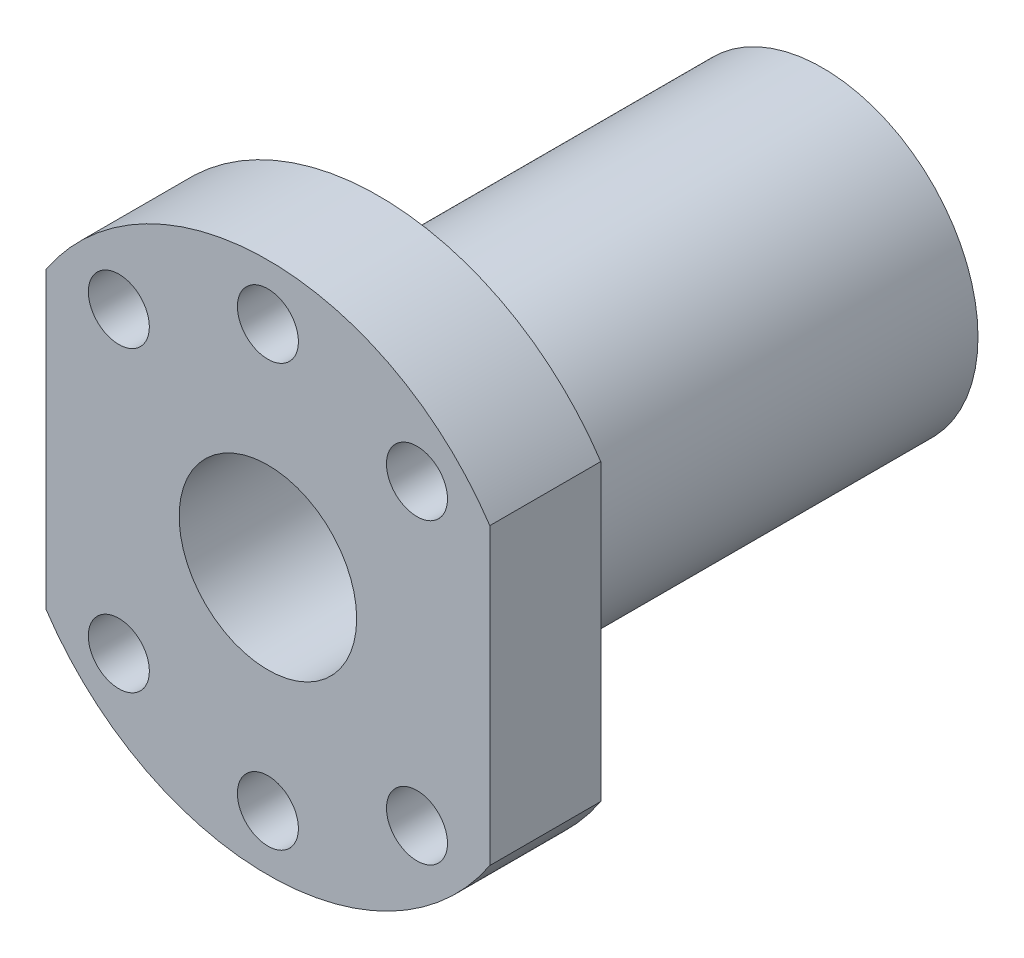
SolidWorks part; units mm, degrees
material "Alloy Steel"
ref_plane "Спереди" through (0, 0, 0) normal (0, 0, 1) x (1, 0, 0)
ref_plane "Сверху" through (0, 0, 0) normal (0, 1, 0) x (1, 0, 0)
ref_plane "Справа" through (0, 0, 0) normal (1, 0, 0) x (0, 0, -1)
sketch "Sketch7" plane through (0, 0, 0) normal (1, 0, 0) x (0, 0, -1)
  line L0 (-22.731, 0) -> (53.4984, 0) construction
  line L1 (0, 8) -> (0, 24)
  line L2 (10, 24) -> (10, 14)
  line L3 (10, 14) -> (50, 14)
  line L4 (50, 14) -> (50, 8)
  line L5 (50, 8) -> (0, 8)
  line L6 (0, 24) -> (10, 24)
  line L7 (5, 19) -> (5, -19) construction
  line L8 (0, 19) -> (10, 19) construction
  point P10 (10, 19)
  point P15 (5, 19)
  point P18 (5, 0)
  dimension "A" = 48
  dimension "L" = 50
  dimension "B" = 10
  dimension "D" = 28
  dimension "dm" = 16
  dimension "W" = 38
revolve "Revolve1" add sketch "Sketch7" angle 360 about L0 other way angle 360
sketch "Sketch8" plane through (0, 0, -10) normal (0, 0, 1) x (1, 0, 0)
  circle A0 centre (0, 0) radius 8 construction
  circle A1 centre (0, 0) radius 8
curve "Helix/Spiral1" pitch 5 height 35 radius 8 centre (0, 0, -10) axis (0, 0, -1) start towards (-0.7071, 0.7071, 0)
ref_plane "Plane1" through (-5.6569, 5.6569, -10) normal (0.7036, 0.7036, -0.099) x (0.7104, -0.6932, 0.1219)
sketch "Sketch9" plane through (-5.6569, 5.6569, -10) normal (0.7036, 0.7036, -0.099) x (0.7104, -0.6932, 0.1219)
  line L0 (0, -2.4488) -> (0, 3.6729) construction
  circle A0 centre (0, 0) radius 1.6
  dimension "D1" = 3.2
sweep "Sweep1" add profiles "Sketch9" path "Helix/Spiral1"
ref_axis "Axis1" through (0, 0, -50) along (0, 0, 1)
sketch "Sketch13" plane through (0, 0, 0) normal (0, 0, 1) x (1, 0, 0)
  line L0 (0, 24) -> (0, -24) construction
  line L1 (-24, 0) -> (24, 0) construction
  line L4 (20, -13.2665) -> (20, 13.2665)
  line L6 (-20, -13.2665) -> (-20, 13.2665)
  circle A0 centre (0, 0) radius 24 construction
  circle A1 centre (0, 0) radius 19 construction
  circle A2 centre (0, 19) radius 2.75
  circle A3 centre (13.435, 13.435) radius 2.75
  circle A4 centre (19, 0) radius 2.75 [skipped]
  circle A5 centre (13.435, -13.435) radius 2.75
  circle A6 centre (0, -19) radius 2.75
  circle A7 centre (-13.435, -13.435) radius 2.75
  circle A8 centre (-19, 0) radius 2.75 [skipped]
  circle A9 centre (-13.435, 13.435) radius 2.75
  arc A10 (20, -13.2665) -> (20, 13.2665) centre (0, 0) ccw
  arc A11 (-20, 13.2665) -> (-20, -13.2665) centre (0, 0) ccw
  point P29 (0, 0)
  dimension "D1" = 38
  dimension "D2" = 5.5
  dimension "D4" = 45
  dimension "D5" = 90
  dimension "H" = 40
  dimension "D6" = 26.533
  dimension "D7" = 26.8701
  dimension "D3" = 8
extrude "Cut-Extrude4" cut sketch "Sketch13" against normal up to next
